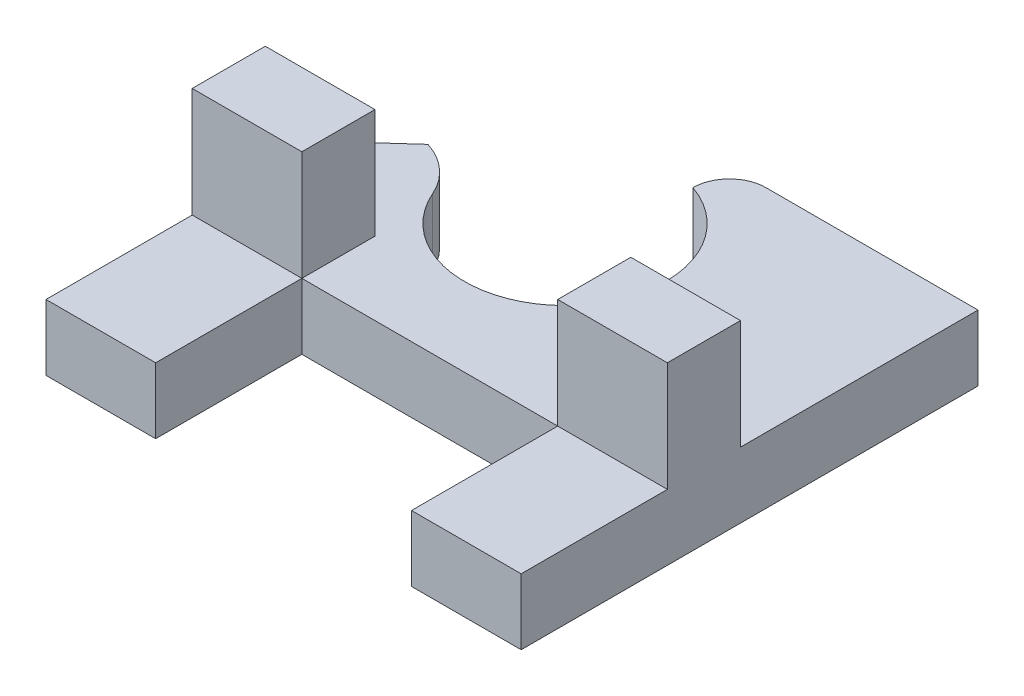
SolidWorks part; units mm, degrees
ref_plane "Front Plane" through (0, 0, 0) normal (0, 0, 1) x (1, 0, 0)
ref_plane "Top Plane" through (0, 0, 0) normal (0, 1, 0) x (1, 0, 0)
ref_plane "Right Plane" through (0, 0, 0) normal (1, 0, 0) x (0, 0, -1)
sketch "Sketch1" plane through (0, 0, 0) normal (0, 1, 0) x (1, 0, 0)
  line L0 (6.5, 2.5) -> (6.5, 0)
  line L1 (3.5, 0) -> (-3.5, 0)
  line L2 (-6.5, 0) -> (-6.5, 2.5)
  line L5 (-6.5, 2.5) -> (-6.5, 3.5)
  line L7 (6.5, 0) -> (6.5, -4)
  line L8 (6.5, -4) -> (3.5, -4)
  line L9 (3.5, 0) -> (3.5, -4)
  line L11 (-6.5, 0) -> (-6.5, -4)
  line L12 (-6.5, -4) -> (-3.5, -4)
  line L13 (-3.5, 0) -> (-3.5, -4)
  line L15 (6.5, 4.9) -> (6.5, 2.5)
  line L17 (-3.95, 4.9) -> (-4.95, 4.9)
  line L18 (-4.95, 4.9) -> (-6.5, 3.5)
  line L19 (-0.3, 7.4986) -> (-0.3, 8.4986)
  line L20 (-0.3, 8.4986) -> (6.5, 8.4986)
  line L21 (6.5, 8.4986) -> (6.5, 4.9)
  arc A2 (-3.95, 4.9) -> (1.55, 4.9) centre (-1.2, 4.9) ccw
  arc A3 (1.55, 4.9) -> (-0.3, 7.4986) centre (-1.2, 4.9) ccw
  point P0 (0, 0)
  dimension "D1" = 2.4
  dimension "D2" = 5.5
  dimension "D3" = 13
  dimension "D4" = 5.3
  dimension "D5" = 2.5
  dimension "D6" = 1
  dimension "D7" = 1
  dimension "D8" = 4
  dimension "D9" = 3
  dimension "D11" = 2.4
  dimension "D12" = 1
  dimension "D13" = 6.8
extrude "Boss-Extrude1" add sketch "Sketch1" along normal blind 1.8
fillet "Fillet1" radius 2 1 edges at (-3.95, 0.9, -4.9)
fillet "Fillet3" radius 1 1 edges at (-0.3, 0.9, -8.4986)
ref_plane "Plane1" through (0, 0, 0) normal (0, -1, 0) x (-1, 0, 0)
sketch "Sketch2" plane through (0, 0, 0) normal (0, -1, 0) x (1, 0, 0)
  line L0 (6.5, 4) -> (6.5, -8.4986) construction
  line L1 (3.5, 0) -> (6.5, 0)
  line L2 (3.5, 0) -> (3.5, -2)
  line L3 (3.5, -2) -> (6.5, -2)
  line L4 (6.5, 0) -> (6.5, -2)
  line L5 (-6.5, -3.5) -> (-6.5, 4) construction
  line L6 (-3.5, 0) -> (-6.5, 0)
  line L7 (-3.5, 0) -> (-3.5, -2)
  line L8 (-3.5, -2) -> (-6.5, -2)
  line L9 (-6.5, 0) -> (-6.5, -2)
  dimension "D1" = 2
extrude "Boss-Extrude2" add sketch "Sketch2" along normal blind 3
mirror "Mirror3" about plane through (0, 0, 0) normal (0, -1, 0) of bodies 104
delete or keep bodies "Body-Delete/Keep 1" type delete bodies bodies 104
